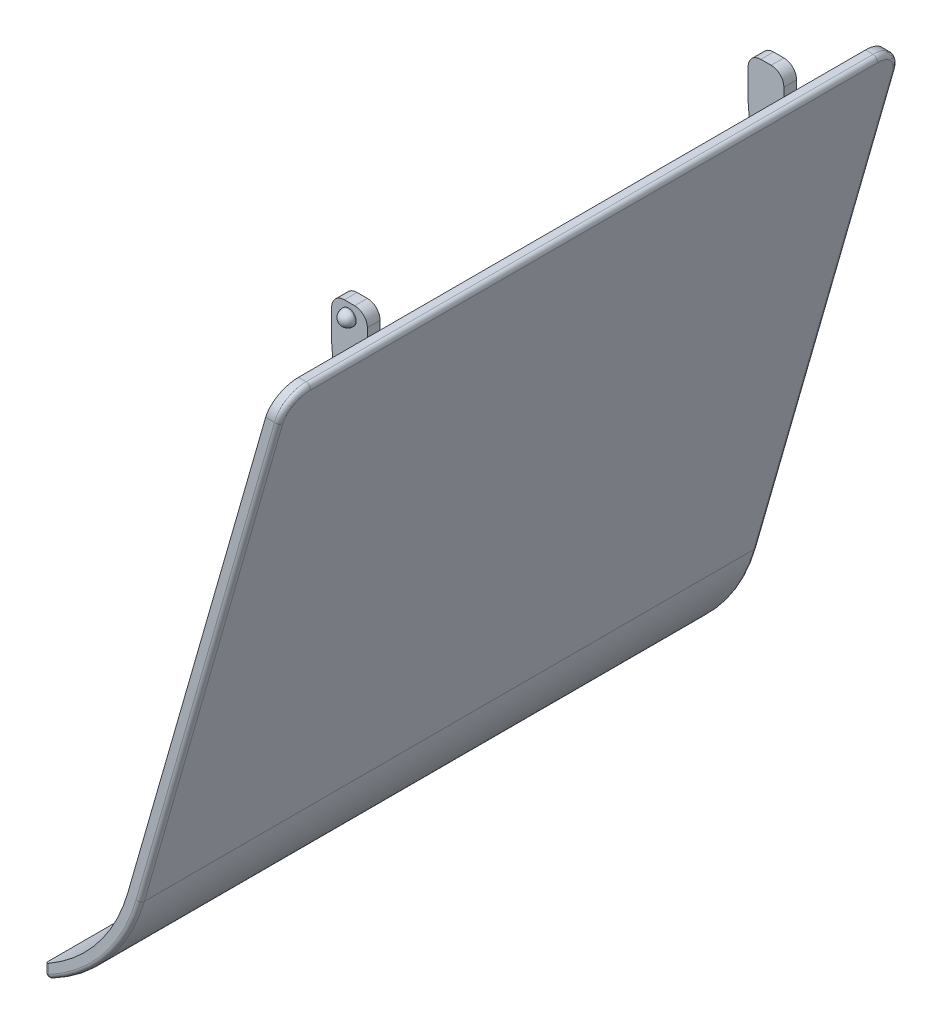
SolidWorks part; units mm, degrees
ref_plane "Front Plane" through (0, 0, 0) normal (0, 0, 1) x (1, 0, 0)
ref_plane "Top Plane" through (0, 0, 0) normal (0, 1, 0) x (1, 0, 0)
ref_plane "Right Plane" through (0, 0, 0) normal (1, 0, 0) x (0, 0, -1)
sketch "Sketch1" plane through (0, 0, 0) normal (0, 0, 1) x (1, 0, 0)
  line L0 (0, 0) -> (-18.2728, 0) construction
  line L1 (0, 0) -> (-17.1109, -59.6727)
  line L2 (0.3169, 1.105) -> (0, 0) construction
  line L3 (1.4419, -0.4135) -> (-15.669, -60.0862)
  line L4 (0, 0) -> (1.5604, 0)
  line L5 (-31.2406, -73.5) -> (-30.8584, -74.9505)
  line L6 (1.7588, 0.6916) -> (1.4419, -0.4135) construction
  line L7 (1.5604, 0) -> (1.4419, -0.4135)
  arc A0 (-30.8584, -74.9505) -> (-15.669, -60.0862) centre (-36.3361, -54.16) ccw
  arc A2 (-31.2406, -73.5) -> (-17.1109, -59.6727) centre (-36.3361, -54.16) ccw
  dimension "D6" = 59.6727
  dimension "D5" = 20
  dimension "D2" = 73.5
  dimension "D1" = 74
  dimension "D4" = 1.5
extrude "Boss-Extrude1" add sketch "Sketch1" along normal mid plane 72.85
sketch "Sketch2" plane through (0, 0, 36.425) normal (0, 0, 1) x (1, 0, 0)
  line L0 (-31.2406, -73.5) -> (-26.9439, -73.5)
  line L1 (-31.2406, -73.5) -> (-30.8584, -74.9505) construction
  line L2 (-31.2406, -73.5) -> (-30.8584, -74.9505)
  arc A0 (-31.2406, -73.5) -> (-17.1109, -59.6727) centre (-36.3361, -54.16) ccw construction
  arc A1 (-30.8584, -74.9505) -> (-15.669, -60.0862) centre (-36.3361, -54.16) ccw construction
  arc A2 (-30.8584, -74.9505) -> (-26.9439, -73.5) centre (-36.3361, -54.16) ccw
extrude "Cut-Extrude1" cut sketch "Sketch2" against normal through all
sketch "Sketch3" plane through (0, 0, 36.425) normal (0, 0, 1) x (1, 0, 0)
  line L0 (-26.9439, -73.5) -> (-31.2406, -73.5) construction
  line L1 (-26.9439, -73.5) -> (-31.2406, -73.5)
  line L2 (-26.9439, -73.5) -> (-26.9439, -71.8175)
  arc A0 (-31.2406, -73.5) -> (-17.1109, -59.6727) centre (-36.3361, -54.16) ccw construction
  arc A1 (-31.2406, -73.5) -> (-26.9439, -71.8175) centre (-36.3361, -54.16) ccw
extrude "Cut-Extrude2" cut sketch "Sketch3" against normal through all
fillet "Fillet1" radius 3 2 edges at (0.7802, 0, -36.425) (0.7802, 0, 36.425)
sketch "Sketch11" plane through (0, 0, 0) normal (0, 0, 1) x (1, 0, 0)
  line L1 (-2.8942, -10.0932) -> (-4.8167, -9.542)
  line L2 (-0.8602, -3) -> (-17.1109, -59.6727) construction
  line L3 (-4.8167, -9.542) -> (-3.3283, -4.3512)
  line L5 (-3.3283, -4.3512) -> (-6.2121, -3.5242)
  line L6 (-6.2121, -3.5242) -> (-8.5274, -11.5988)
  line L7 (-8.5274, -11.5988) -> (-3.7211, -12.977)
  line L8 (-3.7211, -12.977) -> (-2.8942, -10.0932)
  dimension "D1" = 3
  dimension "D2" = 10.5
  dimension "D3" = 5
  dimension "D4" = 3
  dimension "D5" = 8.4
sketch "Sketch27" plane through (0, 0, 0) normal (1, 0, 0) x (0, 0, -1)
  line L0 (-33.425, 0) -> (33.425, 0) construction
  line L1 (-23.8, 2.5) -> (-25.3, 2.5)
  line L2 (-23.8, 2.5) -> (-23.8, -2.5)
  line L3 (-23.8, -2.5) -> (-25.3, -2.5)
  line L4 (-25.3, 2.5) -> (-25.3, -2.5)
  line L5 (-33.425, 0) -> (33.425, 0) construction
  dimension "D1" = 2.5
  dimension "D2" = 23.8
  dimension "D3" = 1.5
  dimension "D4" = 2.5
extrude "Boss-Extrude12" add sketch "Sketch27" along normal up to surface (4.9269 mm away) from offset 4.21
sketch "Sketch30" plane through (0, 0, 25.3) normal (0, 0, 1) x (1, 0, 0)
  line L1 (0.7169, 2.5) -> (0, 2.5)
  line L2 (0.7169, 2.5) -> (0.7169, 0)
  line L3 (0.7169, 0) -> (0, 0)
  line L4 (0, 2.5) -> (0, 0)
extrude "Cut-Extrude9" cut sketch "Sketch30" against normal up to next
sketch "Sketch31" plane through (0, 0, 25.3) normal (0, 0, 1) x (1, 0, 0)
  line L0 (0, 2.5) -> (-4.21, 2.5) construction
  line L1 (-4.21, 2.5) -> (-4.21, -2.5) construction
  circle A0 centre (-2.21, 1) radius 0.9
  dimension "D3" = 1.8
  dimension "D1" = 1.5
  dimension "D2" = 2
extrude "Boss-Extrude13" add sketch "Sketch31" along normal blind 1
fillet "Fillet9" radius 1.5 1 edges at (-4.21, 2.5, 24.55)
fillet "Fillet10" radius 1.5 1 edges at (0, 2.5, 24.55)
fillet "Fillet11" radius 0.9 1 edges at (-1.31, 1, 26.3)
mirror "Mirror4" about plane through (0, 0, 0) normal (0, 0, 1) of "Fillet11", "Fillet10", "Fillet9", "Boss-Extrude13", "Cut-Extrude9", "Boss-Extrude12"
fillet "Fillet12" radius 0.5 10 edges at (-19.8779, -67.9939, 36.425) (-7.4844, -31.5431, 36.425) (1.3085, -0.8787, 35.5463) (-19.8779, -67.9939, -36.425) (-7.4844, -31.5431, -36.425) (1.3085, -0.8787, -35.5463) (-26.9439, -72.6587, -36.425) (-26.9439, -72.6587, 36.425) (-26.9439, -73.5, 0) (1.5604, 0, 0)
chamfer "Chamfer1" distance 3.5 distance2 10 2 edges at (-0.7169, -2.5, 24.55) (-0.7169, -2.5, -24.55)
